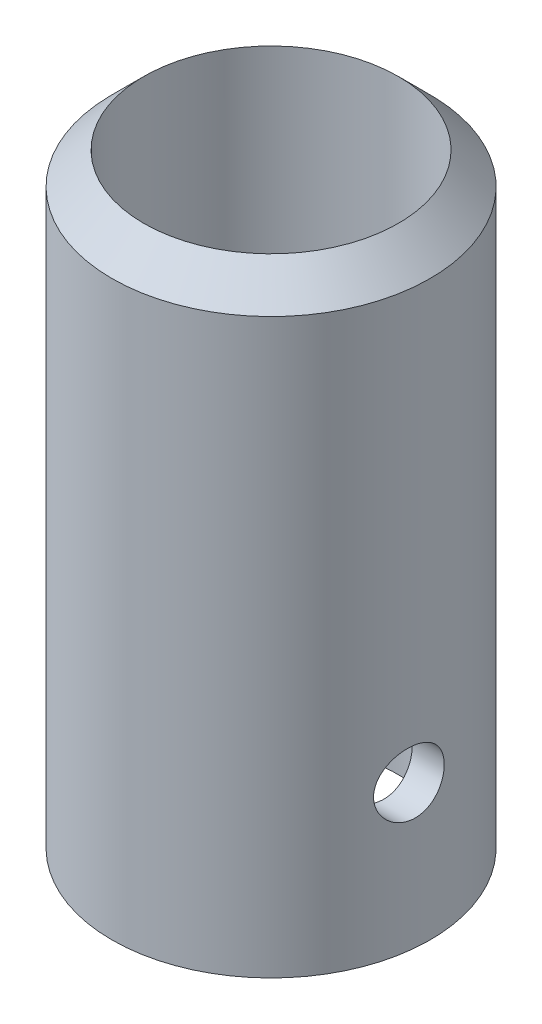
SolidWorks part; units mm, degrees
ref_plane "Front Plane" through (0, 0, 0) normal (0, 0, 1) x (1, 0, 0)
ref_plane "Top Plane" through (0, 0, 0) normal (0, 1, 0) x (1, 0, 0)
ref_plane "Right Plane" through (0, 0, 0) normal (1, 0, 0) x (0, 0, -1)
sketch "Sketch2" plane through (0, 0, 0) normal (0, 1, 0) x (1, 0, 0)
  circle A0 centre (72.5817, 46.8465) radius 25
  dimension "D1" = 50
extrude "Boss-Extrude2" add sketch "Sketch2" along normal blind 100
sketch "Sketch3" plane through (0, 100, 0) normal (0, 1, 0) x (1, 0, 0)
  circle A0 centre (72.5817, 46.8465) radius 20
  dimension "D1" = 40
extrude "Cut-Extrude1" cut sketch "Sketch3" against normal through all
chamfer "Chamfer2" distance 10 angle 45 1 edges at (72.5817, 100, -21.8465)
sketch "Sketch4" plane through (0, 0, 0) normal (1, 0, 0) x (0, 0, -1)
  circle A0 centre (44.1615, 22.6514) radius 5
extrude "Cut-Extrude3" cut sketch "Sketch4" along normal through all
